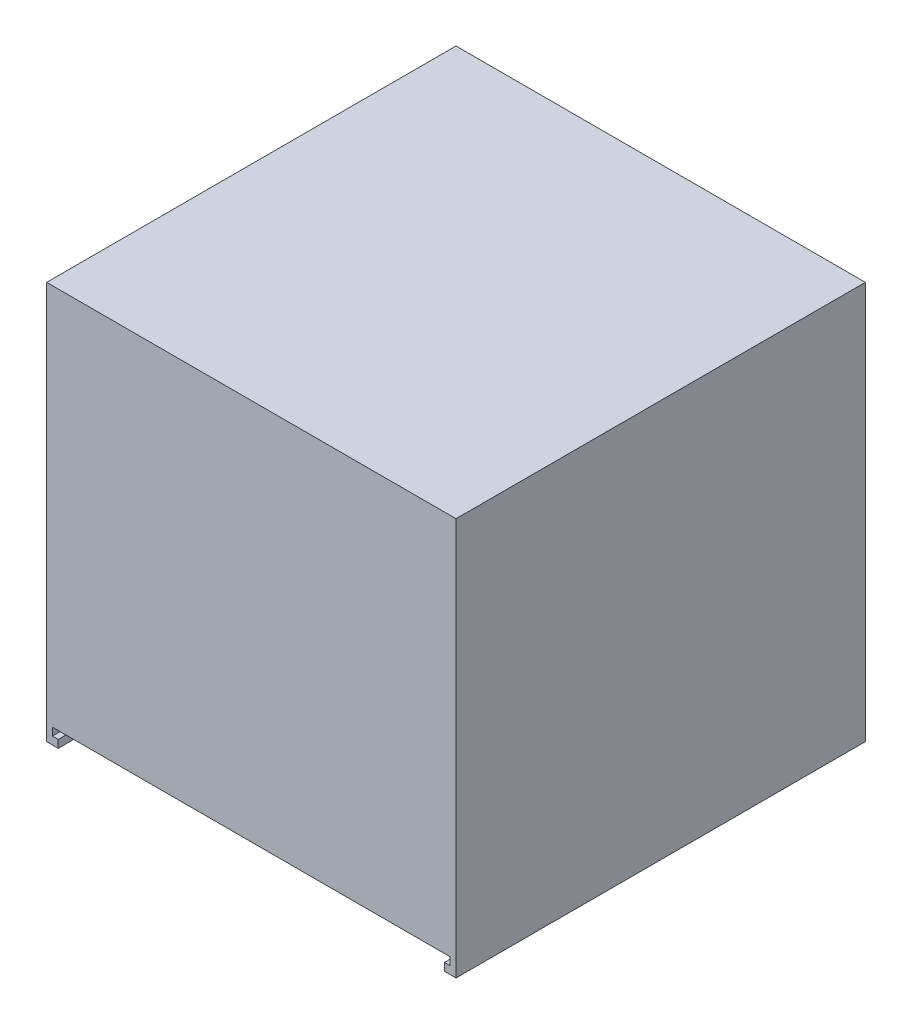
SolidWorks part; units mm, degrees
ref_plane "Front Plane" through (0, 0, 0) normal (0, 0, 1) x (1, 0, 0)
ref_plane "Top Plane" through (0, 0, 0) normal (0, 1, 0) x (1, 0, 0)
ref_plane "Right Plane" through (0, 0, 0) normal (1, 0, 0) x (0, 0, -1)
sketch "Sketch1" plane through (0, 0, 0) normal (0, 1, 0) x (1, 0, 0)
  line L0 (-53, 53) -> (53, 53)
  line L1 (-50, -50) -> (50, -50)
  line L2 (-50, -50) -> (-50, 50)
  line L3 (-50, 50) -> (50, 50)
  line L4 (50, -50) -> (50, 50)
  line L5 (-50, -50) -> (50, 50) construction
  line L6 (-50, 50) -> (50, -50) construction
  line L11 (53, -53) -> (53, 53)
  line L12 (-53, -53) -> (53, -53)
  line L13 (-53, -53) -> (-53, 53)
  point P0 (0, 0)
  dimension "D2" = 100
  dimension "D1" = 3
extrude "Boss-Extrude1" add sketch "Sketch1" along normal blind 100
sketch "Sketch2" plane through (0, 100, 0) normal (0, 1, 0) x (1, 0, 0)
  line L1 (-53, -53) -> (53, -53)
  line L2 (-53, -53) -> (-53, 53)
  line L3 (-53, 53) -> (53, 53)
  line L4 (53, -53) -> (53, 53)
extrude "Boss-Extrude2" add sketch "Sketch2" along normal blind 3
sketch "Sketch4" plane through (0, 0, 53) normal (0, 0, 1) x (1, 0, 0)
  line L0 (-53, 103) -> (-53, 0) construction
  line L1 (-51.5, 2) -> (51.5, 2)
  line L2 (-51.5, 2) -> (-51.5, 4)
  line L3 (-51.5, 4) -> (51.5, 4)
  line L4 (51.5, 2) -> (51.5, 4)
  line L5 (53, 103) -> (53, 0) construction
  line L6 (-53, 0) -> (53, 0) construction
  dimension "D1" = 1.5
  dimension "D2" = 1.5
  dimension "D3" = 2
  dimension "D4" = 2
extrude "Cut-Extrude1" cut sketch "Sketch4" against normal offset from surface (104 mm away) 2 up to face at (0, 51.5, -53)
sketch "Sketch5" plane through (0, 0, 53) normal (0, 0, 1) x (1, 0, 0)
  line L0 (-53, 0) -> (53, 0) construction
  line L1 (-50, 2) -> (50, 2)
  line L2 (-50, 2) -> (-50, 0)
  line L3 (-50, 0) -> (50, 0)
  line L4 (50, 2) -> (50, 0)
  line L5 (50, 2) -> (50, 0) construction
extrude "Cut-Extrude2" cut sketch "Sketch5" against normal up to next
sketch "Sketch6" plane through (0, 0, -53) normal (0, 0, -1) x (-1, 0, 0)
  line L0 (-25, 75) -> (25, 75) construction
  line L1 (-53, 0) -> (53, 0) construction
  line L2 (-27.8423, 31.5617) -> (-25.0139, 34.3901)
  line L3 (27.8145, 31.5197) -> (24.9861, 34.3482)
  circle A0 centre (-25, 75) radius 7.5
  circle A1 centre (25, 75) radius 7.5
  arc A2 (-25.0139, 34.3901) -> (24.9861, 34.3482) centre (0, 50.9523) ccw
  arc A3 (-27.8423, 31.5617) -> (27.8145, 31.5197) centre (0, 50) ccw
  point P4 (0, 75)
  point P14 (-23.0673, 41.3861)
  point P15 (17.972, 41.3861)
  point P16 (-26.8551, 35.5219)
  point P17 (25, 33.0284)
  point P18 (-19.8308, 35.9183)
  point P19 (0, 0)
  point P20 (0, 0)
  point P21 (0, 0)
  point P22 (25, 32.2693)
  point P23 (27.8484, 31.8454)
  point P24 (0, 0)
  point P25 (-25, 34.3482)
  dimension "D1" = 15
  dimension "D6" = 30
  dimension "D2" = 50
  dimension "D3" = 75
  dimension "D4" = 315
  dimension "D5" = 4
  dimension "D7" = 50
  dimension "D8" = 50
extrude "Cut-Extrude3" cut sketch "Sketch6" against normal up to next
